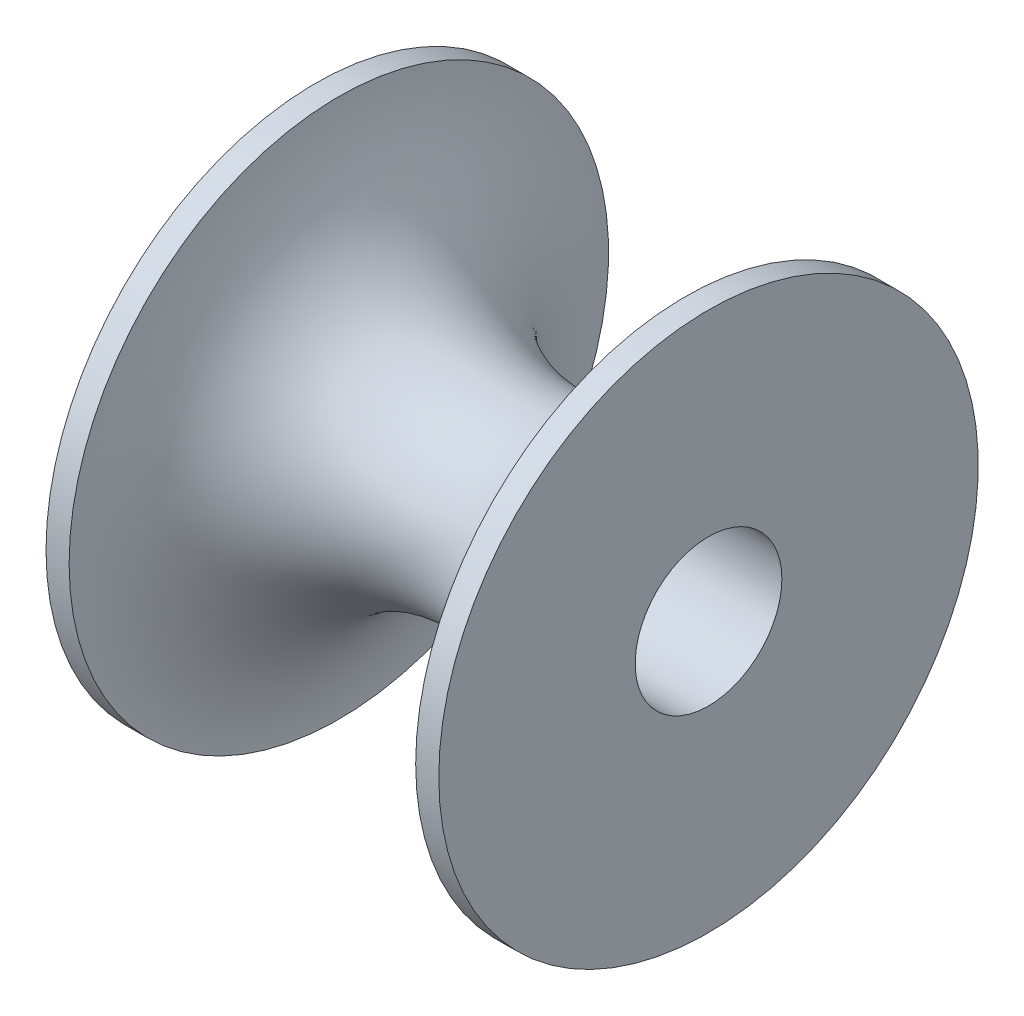
SolidWorks part; units mm, degrees
ref_plane "Front Plane" through (0, 0, 0) normal (0, 0, 1) x (1, 0, 0)
ref_plane "Top Plane" through (0, 0, 0) normal (0, 1, 0) x (1, 0, 0)
ref_plane "Right Plane" through (0, 0, 0) normal (1, 0, 0) x (0, 0, -1)
sketch "Sketch1" plane through (0, 0, 0) normal (0, 1, 0) x (1, 0, 0)
  line L0 (-15, 0) -> (-17, 0)
  line L1 (-17, 0) -> (-17, 23.35)
  line L2 (-17, 23.35) -> (17, 23.35)
  line L3 (17, 23.35) -> (17, 0)
  line L4 (17, 0) -> (15, 0)
  line L5 (-17, 15) -> (17, 15) construction
  line L6 (-17, 17) -> (17, 17) construction
  arc A0 (-15, 0) -> (15, 0) centre (0, 0) cw
  circle A1 centre (0, 0) radius 14.2875 construction
  dimension "D1" = 15
  dimension "D3" = 28.575
  dimension "D4" = 2
  dimension "D2" = 30
  dimension "D5" = 2
  dimension "D6" = 6.35
revolve "Revolve1" add sketch "Sketch1" angle 360 about L2
sketch "Sketch2" plane through (17, 0, 0) normal (1, 0, 0) x (0, 0, -1)
  circle A0 centre (23.35, 0) radius 6.35
  dimension "D1" = 12.7
extrude "Cut-Extrude1" cut sketch "Sketch2" against normal up to surface (34 mm away) up to face at (-17, 0, 0)
ref_plane "mid wheel" through (0, 0, 0) normal (1, 0, 0) x (0, 0, -1)
